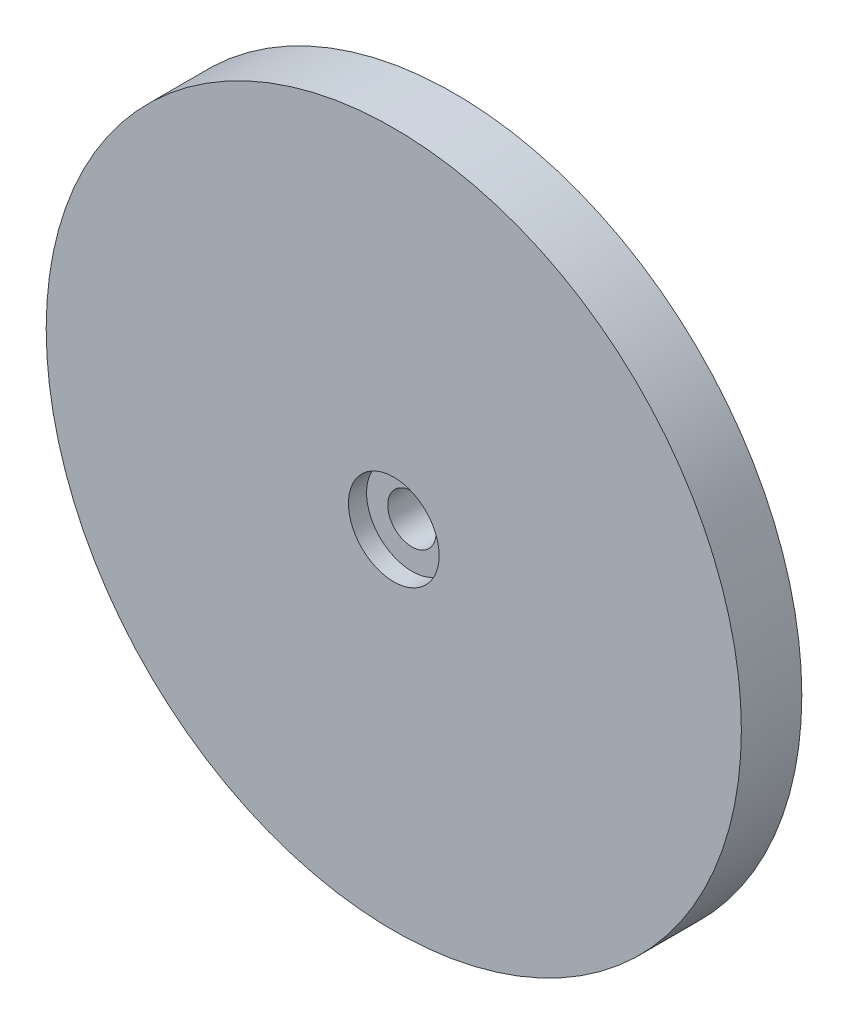
SolidWorks part; units mm, degrees
ref_plane "Front Plane" through (0, 0, 0) normal (0, 0, 1) x (1, 0, 0)
ref_plane "Top Plane" through (0, 0, 0) normal (0, 1, 0) x (1, 0, 0)
ref_plane "Right Plane" through (0, 0, 0) normal (1, 0, 0) x (0, 0, -1)
sketch "Sketch1" plane through (0, 0, 0) normal (0, 0, 1) x (1, 0, 0)
  circle A0 centre (0, 0) radius 57.5
  dimension "D1" = 115
extrude "Boss-Extrude1" add sketch "Sketch1" along normal blind 10
sketch "Sketch2" plane through (0, 0, 10) normal (0, 0, 1) x (1, 0, 0)
  circle A0 centre (0, 0) radius 4
  circle A1 centre (0, 0) radius 7.5
  dimension "D1" = 8
  dimension "D2" = 15
extrude "Cut-Extrude1" cut sketch "Sketch2" against normal blind 3
extrude "Cut-Extrude2" cut sketch "Sketch2<2>" against normal through all contours A0 region at (0, 0, 10)
sketch "Sketch2<2>" plane through (0, 0, 10) normal (0, 0, 1) x (1, 0, 0) same geometry as "Sketch2"
